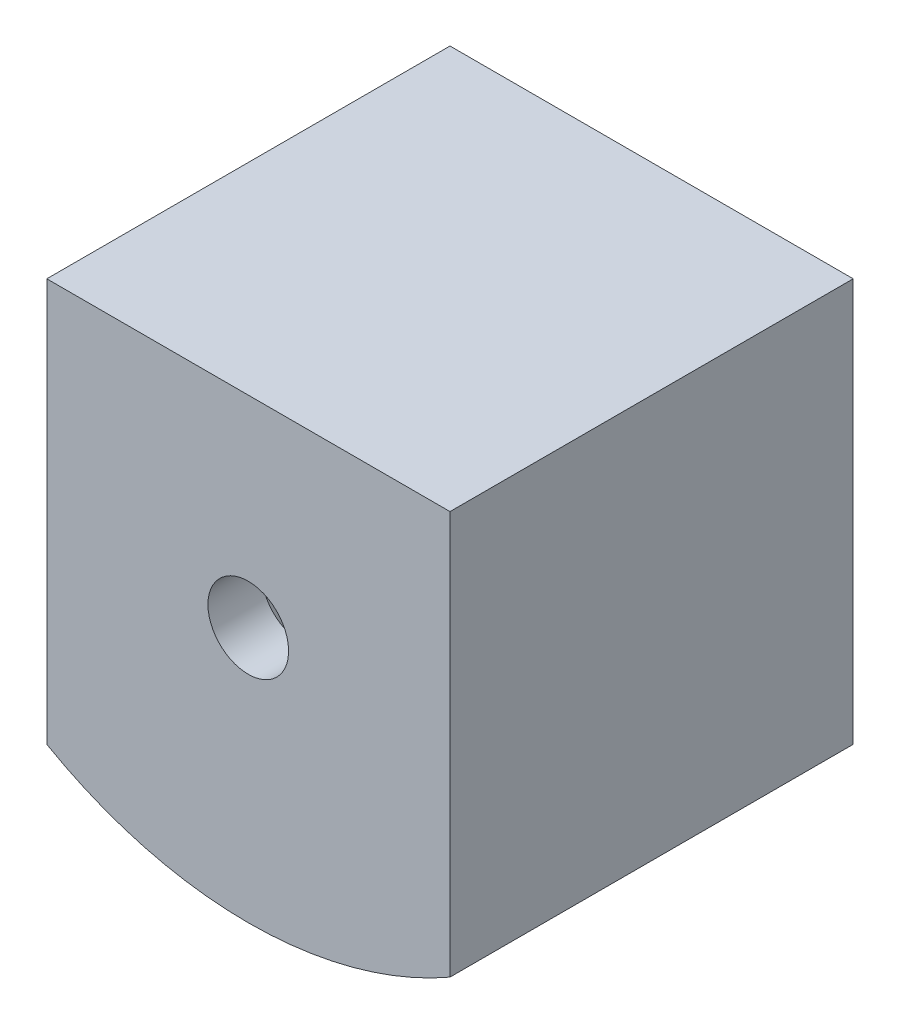
SolidWorks part; units mm, degrees
ref_plane "Front Plane" through (0, 0, 0) normal (0, 0, 1) x (1, 0, 0)
ref_plane "Top Plane" through (0, 0, 0) normal (0, 1, 0) x (1, 0, 0)
ref_plane "Right Plane" through (0, 0, 0) normal (1, 0, 0) x (0, 0, -1)
sketch "Sketch1" plane through (0, 0, 0) normal (0, 0, 1) x (1, 0, 0)
  line L2 (15, -15) -> (15, 15)
  line L3 (15, 15) -> (-15, 15)
  line L4 (-15, -15) -> (-15, 15)
  line L5 (15, -15) -> (-15, 15) construction
  line L6 (15, 15) -> (-15, -15) construction
  arc A3 (-15, -15) -> (15, -15) centre (0, 11.0898) ccw
  point P0 (0, 0)
extrude "Boss-Extrude1" add sketch "Sketch1" along normal blind 30
shell "Shell13" thickness 4 removed face at (0, -1.0012, 0)
sketch "Sketch3" plane through (0, 0, 26) normal (0, 0, -1) x (-1, 0, 0)
  circle A0 centre (0.0103, 0.0076) radius 3
extrude "Cut-Extrude2" cut sketch "Sketch3" against normal blind 4
sketch "Sketch4" plane through (0, 0, 0) normal (0, 0, -1) x (-1, 0, 0)
  line L0 (-14.5226, 2.3) -> (-11.5226, 2.3)
  line L5 (-14.5, 11.1) -> (-11.5, 11.1)
  line L6 (-14.5, 11.1) -> (-14.5, 3.1)
  line L7 (-14.5, 3.1) -> (-11.5, 3.1)
  line L8 (-11.5, 11.1) -> (-11.5, 3.1)
  line L17 (-11, -12.5729) -> (-11, 11) construction
  line L18 (-14.5226, 2.3) -> (-14.5226, -5.7)
  line L19 (-14.5226, -5.7) -> (-11.5226, -5.7)
  line L20 (-11.5226, 2.3) -> (-11.5226, -5.7)
  line L21 (-11, 11) -> (11, 11) construction
  line L22 (-14.5693, -6.5) -> (-11.5693, -6.5)
  line L23 (-14.5693, -6.5) -> (-14.5693, -14.5)
  line L24 (-14.5693, -14.5) -> (-11.5693, -14.5)
  line L25 (-11.5693, -6.5) -> (-11.5693, -14.5)
  line L26 (14.4575, -14.531) -> (11.4575, -14.5246)
  line L28 (14.4467, 2.2691) -> (14.4296, -5.7309)
  line L29 (14.4296, -5.7309) -> (11.4296, -5.7245)
  line L30 (11.4467, 2.2755) -> (11.4296, -5.7245)
  line L31 (14.4467, 2.2691) -> (11.4467, 2.2755)
  line L32 (14.4258, 3.0691) -> (11.4258, 3.0755)
  line L33 (14.4428, 11.0691) -> (14.4258, 3.0691)
  line L34 (14.4428, 11.0691) -> (11.4428, 11.0755)
  line L35 (11.4428, 11.0755) -> (11.4258, 3.0755)
  line L36 (14.4746, -6.531) -> (14.4575, -14.531)
  line L37 (14.4746, -6.531) -> (11.4746, -6.5246)
  line L38 (11.4746, -6.5246) -> (11.4575, -14.5246)
  point P15 (-0.0382, 2.1143)
  point P20 (0, 0)
  dimension "D1" = 0.8
  dimension "D2" = 0.5
  dimension "D3" = 0.1
  dimension "D4" = 0.8
extrude "Cut-Extrude3" cut sketch "Sketch4" against normal blind 27
